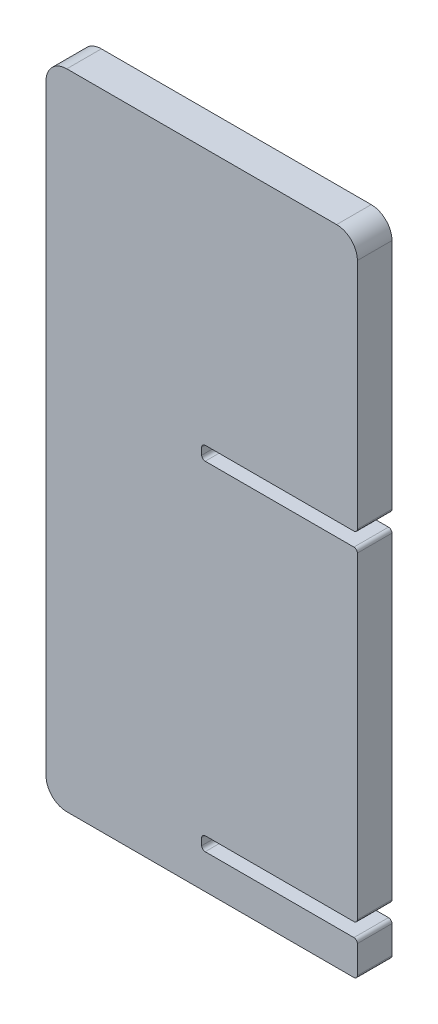
SolidWorks part; units mm, degrees
ref_plane "Alzado" through (0, 0, 0) normal (0, 0, 1) x (1, 0, 0)
ref_plane "Planta" through (0, 0, 0) normal (0, 1, 0) x (1, 0, 0)
ref_plane "Vista lateral" through (0, 0, 0) normal (1, 0, 0) x (0, 0, -1)
sketch "Croquis1" plane through (0, 0, 0) normal (0, 0, 1) x (1, 0, 0)
  line L1 (-22.5, 45) -> (22.5, 45)
  line L2 (-22.5, 45) -> (-22.5, -48)
  line L3 (-22.5, -48) -> (22.5, -48)
  line L4 (22.5, 45) -> (22.5, -48)
  dimension "D1" = 45
  dimension "D2" = 22.5
  dimension "D3" = 93
  dimension "D4" = 45
extrude "Saliente-Extruir1" add sketch "Croquis1" along normal blind 5 contours L2 L3 L4 L1
sketch "Croquis2" plane through (0, 0, 5) normal (0, 0, 1) x (1, 0, 0)
  line L0 (22.5, 45) -> (22.5, -48) construction
  line L1 (22.5, 7.8795) -> (0, 7.8795)
  line L2 (22.5, 7.8795) -> (22.5, 5.8795)
  line L3 (22.5, 5.8795) -> (0, 5.8795)
  line L4 (0, 7.8795) -> (0, 5.8795)
  dimension "D1" = 22.5
  dimension "D2" = 2
  dimension "D3" = 5.8795
extrude "Cortar-Extruir1" cut sketch "Croquis2" against normal up to surface (5 mm away) up to face at (0, -1.5, 0)
sketch "Croquis3" plane through (0, 0, 5) normal (0, 0, 1) x (1, 0, 0)
  line L0 (22.5, 5.8795) -> (22.5, -48) construction
  line L1 (22.5, -41) -> (0, -41)
  line L2 (22.5, -41) -> (22.5, -43)
  line L3 (22.5, -43) -> (0, -43)
  line L4 (0, -41) -> (0, -43)
  line L5 (-22.5, -48) -> (22.5, -48) construction
  dimension "D1" = 2
  dimension "D2" = 5
  dimension "D3" = 22.5
extrude "Cortar-Extruir2" cut sketch "Croquis3" against normal up to surface (5 mm away) up to face at (5.625, 2.6897, 0)
fillet "Redondeo1" radius 3 3 edges at (-22.5, -48, 2.5) (22.5, 45, 2.5) (-22.5, 45, 2.5)
fillet "Redondeo2" radius 0.5 9 edges at (22.5, 5.8795, 2.5) (22.5, 7.8795, 2.5) (0, 7.8795, 2.5) (0, 5.8795, 2.5) (22.5, -43, 2.5) (0, -43, 2.5) (0, -41, 2.5) (22.5, -41, 2.5) (22.5, -48, 2.5)
